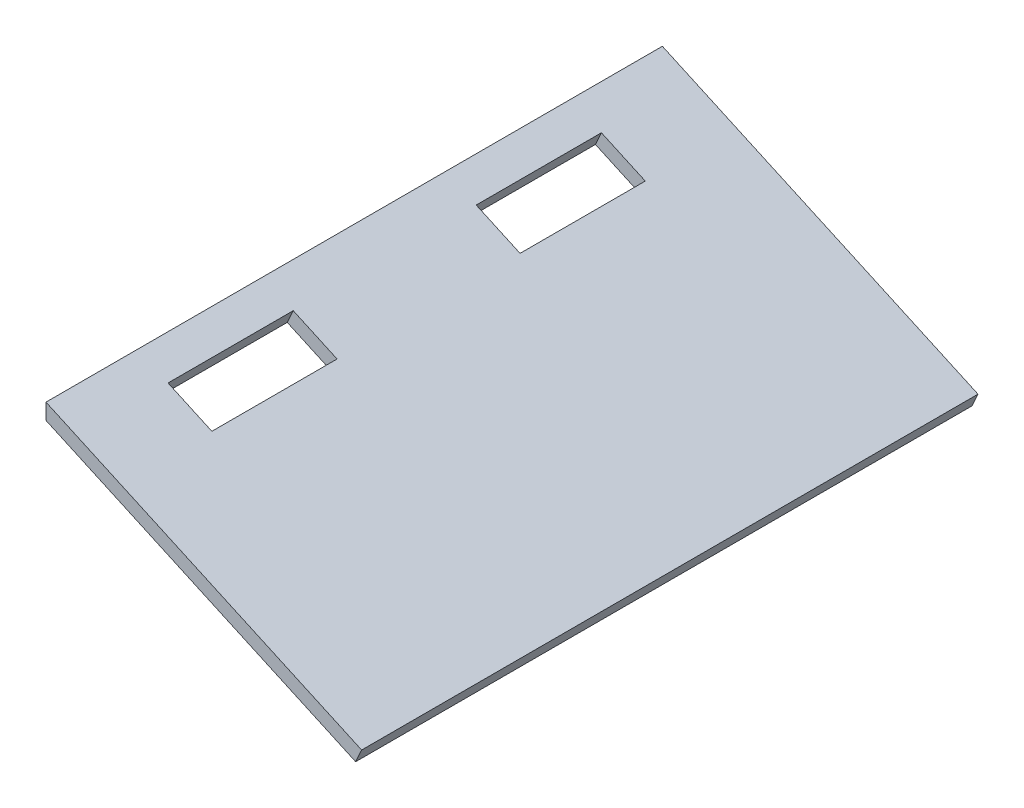
SolidWorks part; units mm, degrees
material "Pine"
ref_plane "Front Plane" through (0, 0, 0) normal (0, 0, 1) x (1, 0, 0)
ref_plane "Top Plane" through (0, 0, 0) normal (0, 1, 0) x (1, 0, 0)
ref_plane "Right Plane" through (0, 0, 0) normal (1, 0, 0) x (0, 0, -1)
sketch "Sketch3" plane through (0, 0, 0) normal (0, 0, 1) x (1, 0, 0)
  line L0 (-108.5345, -3.9032) -> (-108.5345, 1464.0363)
  line L1 (-108.5345, -3.9032) -> (-870.5345, -3.9032)
  line L2 (-870.5345, -3.9032) -> (-870.5345, 625.8363)
  line L3 (-972.1345, 737.9573) -> (-972.1345, 834.2968)
  line L4 (-768.9345, 834.2968) -> (-768.9345, 986.6968)
  line L5 (-972.1345, 834.2968) -> (-768.9345, 834.2968)
  line L6 (-528.0858, 1843.9468) -> (-737.1845, 1843.9468)
  line L7 (-968.4148, 728.977) -> (-874.2542, 634.8165)
  line L8 (-737.1845, 1672.0154) -> (-737.1845, 1762.6932)
  line L9 (-520.195, 1875.6968) -> (-756.2345, 1875.6968)
  line L10 (-112.2542, 1473.0165) -> (-511.2148, 1871.977)
  line L11 (-737.1845, 1692.941) -> (-241.631, 1467.6894)
  line L12 (-596.8655, 1608.234) -> (-737.1845, 983.1768)
  line L13 (-763.9746, 985.3593) -> (-203.7845, 834.2968)
  line L14 (-761.4898, 1669.1128) -> (-638.6318, 1613.2683)
  line L15 (-631.4955, 1598.9249) -> (-768.9345, 986.6968)
  line L16 (-768.9345, 1680.6745) -> (-768.9345, 1862.9968)
  line L17 (-737.1845, 1780.4468) -> (-737.1845, 1843.9468)
  line L18 (-737.1845, 1692.941) -> (-737.1845, 1843.9468) construction
  line L19 (-737.1845, 1692.941) -> (-737.1845, 1762.6932) construction
  line L20 (-838.7845, -3.9032) -> (-838.7845, 834.2968)
  line L21 (-745.0674, 1675.5986) -> (-249.5139, 1450.347) construction
  line L22 (-140.2845, -3.9032) -> (-140.2845, 1456.1455)
  line L23 (-140.2845, 1456.1455) -> (-528.0858, 1843.9468)
  line L24 (-537.8111, 1581.3911) -> (-673.6845, 976.1369)
  line L25 (-768.9345, 966.9663) -> (-203.7845, 814.5663)
  line L26 (-737.1845, 1672.0154) -> (-203.7845, 1429.5608)
  line L27 (-528.0858, 1843.9468) -> (-554.3883, 1780.4468)
  line L28 (-140.2845, 1456.1455) -> (-203.7845, 1429.8429)
  line L29 (-775.2845, -3.9032) -> (-775.2845, 834.2968)
  line L30 (-773.8944, 968.3038) -> (-208.7444, 815.9038) construction
  line L31 (-203.7845, -3.9032) -> (-203.7845, 1429.8429)
  line L32 (-203.7845, 1429.8429) -> (-554.3883, 1780.4468)
  line L33 (-554.3883, 1780.4468) -> (-737.1845, 1780.4468)
  line L34 (-768.9345, 966.9663) -> (-763.9746, 985.3593)
  line L35 (-737.1845, 1762.6932) -> (-369.5099, 1595.5683)
  line L36 (-673.6845, 1733.8295) -> (-599.2171, 1699.9807) construction
  line L37 (-737.1845, 1692.941) -> (-625.4936, 1642.1724) construction
  line L38 (-538.5586, 1578.0615) -> (-673.6845, 976.1369) construction
  line L39 (-600.5166, 1591.9704) -> (-737.1845, 983.1768) construction
  line L40 (-554.3883, 1780.4468) -> (-673.6845, 1780.4468) construction
  line L41 (-203.7845, 91.3468) -> (-203.7845, 1429.8429) construction
  line L42 (-140.2845, 27.8468) -> (-140.2845, 1456.1455) construction
  line L43 (-775.2845, 91.3468) -> (-775.2845, 625.8363) construction
  line L44 (-838.7845, 27.8468) -> (-838.7845, 625.8363) construction
  line L45 (-203.7845, 91.3468) -> (-775.2845, 91.3468) construction
  line L46 (-140.2845, 27.8468) -> (-838.7845, 27.8468) construction
  line L47 (-940.3845, 745.8481) -> (-851.8036, 657.2672) construction
  line L48 (-843.7807, 739.0468) -> (-806.9023, 702.1685) construction
  line L49 (-843.7807, 739.0468) -> (-673.6845, 739.0468) construction
  line L50 (-940.3845, 802.5468) -> (-737.1845, 802.5468) construction
  line L51 (-940.3845, 745.8481) -> (-940.3845, 802.5468) construction
  line L52 (-843.7807, 739.0468) -> (-843.7807, 739.0468) construction
  line L53 (-673.6845, 1733.8295) -> (-673.6845, 1780.4468) construction
  line L54 (-756.2345, 1692.941) -> (-756.2345, 1792.2779) construction
  line L55 (-756.2345, 1792.2779) -> (-361.627, 1612.9108) construction
  line L56 (-673.6845, 739.0468) -> (-673.6845, 976.1369) construction
  line L57 (-737.1845, 802.5468) -> (-737.1845, 983.1768) construction
  line L58 (-768.9345, 986.6968) -> (-203.7845, 834.2968) construction
  line L59 (-203.7845, 834.2968) -> (-208.7444, 815.9038)
  line L60 (-768.9345, 901.198) -> (-203.7845, 748.798)
  line L61 (-846.7775, 922.1894) -> (-163.9675, 738.0608) construction
  line L62 (-768.9345, 966.9663) -> (-208.7444, 815.9038) construction
  line L64 (-808.7515, 1063.2022) -> (-125.9415, 879.0737) construction
  line L65 (-125.9415, 879.0737) -> (-163.9675, 738.0608) construction
  line L66 (-846.7775, 922.1894) -> (-808.7515, 1063.2022) construction
  arc A0 (-108.5345, 1464.0363) -> (-112.2542, 1473.0165) centre (-121.2345, 1464.0363) ccw
  arc A1 (-511.2148, 1871.977) -> (-520.195, 1875.6968) centre (-520.195, 1862.9968) ccw
  arc A2 (-768.9345, 1862.9968) -> (-756.2345, 1875.6968) centre (-756.2345, 1862.9968) cw
  arc A3 (-768.9345, 1680.6745) -> (-761.4898, 1669.1128) centre (-756.2345, 1680.6745) ccw
  arc A4 (-631.4955, 1598.9249) -> (-638.6318, 1613.2683) centre (-643.8871, 1601.7067) ccw
  arc A5 (-972.1345, 737.9573) -> (-968.4148, 728.977) centre (-959.4345, 737.9573) ccw
  arc A6 (-870.5345, 625.8363) -> (-874.2542, 634.8165) centre (-883.2345, 625.8363) ccw
  arc A7 (-737.1845, 1843.9468) -> (-737.1845, 1843.9468) centre (-737.1845, 1843.9468) cw
  arc A8 (-737.1845, 1692.941) -> (-737.1845, 1692.941) centre (-737.1845, 1692.941) ccw
  arc A12 (-140.2845, 1456.1455) -> (-140.2845, 1456.1455) centre (-140.2845, 1456.1455) ccw
  arc A13 (-528.0858, 1843.9468) -> (-528.0858, 1843.9468) centre (-528.0858, 1843.9468) ccw
  arc A14 (-600.5166, 1591.9704) -> (-625.4936, 1642.1724) centre (-643.8871, 1601.7067) ccw construction
  arc A16 (-203.7845, 1429.8429) -> (-203.7845, 1429.8429) centre (-203.7845, 1429.8429) ccw
  arc A17 (-554.3883, 1780.4468) -> (-554.3883, 1780.4468) centre (-554.3883, 1780.4468) ccw
  arc A18 (-673.6845, 1780.4468) -> (-673.6845, 1780.4468) centre (-673.6845, 1780.4468) cw
  arc A19 (-673.6845, 1733.8295) -> (-673.6845, 1733.8295) centre (-673.6845, 1733.8295) ccw
  arc A20 (-838.7845, 625.8363) -> (-851.8036, 657.2672) centre (-883.2345, 625.8363) ccw construction
  arc A21 (-775.2845, 625.8363) -> (-806.9023, 702.1685) centre (-883.2345, 625.8363) ccw construction
  arc A22 (-843.7807, 739.0468) -> (-843.7807, 739.0468) centre (-843.7807, 739.0468) ccw construction
  arc A23 (-940.3845, 745.8481) -> (-940.3845, 745.8481) centre (-940.3845, 745.8481) ccw construction
  arc A24 (-756.2345, 1692.941) -> (-745.0674, 1675.5986) centre (-737.1845, 1692.941) ccw construction
  dimension "D1" = 12.7
  dimension "D2" = 31.75
  dimension "D3" = 63.5
  dimension "D4" = 19.05
  dimension "D5" = 19.05
  dimension "D6" = 63.5
sketch "Sketch6" plane through (0, 0, 0) normal (0, 0, 1) x (1, 0, 0)
  line L0 (-737.1845, 1672.0154) -> (-737.1845, 1692.941)
  line L1 (-737.1845, 1692.941) -> (-320.9649, 1503.7503)
  line L2 (-737.1845, 1672.0154) -> (-328.8479, 1486.4078)
  line L5 (-320.9649, 1503.7503) -> (-328.8479, 1486.4078)
extrude "Boss-Extrude1" add sketch "Sketch6" along normal blind 812.8
sketch "Sketch7" plane through (503.6386, 1108.0049, 0) normal (-0.4138, -0.9104, 0) x (0.9104, -0.4138, 0)
  line L0 (-1362.9929, 0) -> (-914.452, 0)
  line L1 (-914.452, 812.8) -> (-914.452, 0) construction
  line L2 (-1362.9929, 812.8) -> (-1362.9929, 0)
  line L3 (-914.452, 812.8) -> (-914.452, 0)
  line L4 (-1056.1725, 641.35) -> (-1056.1725, 577.85)
  line L5 (-1221.2725, 171.45) -> (-1056.1725, 171.45)
  line L6 (-1221.2725, 171.45) -> (-1221.2725, 234.95)
  line L7 (-1221.2725, 234.95) -> (-1056.1725, 234.95)
  line L8 (-1056.1725, 171.45) -> (-1056.1725, 234.95)
  line L9 (-1221.2725, 577.85) -> (-1056.1725, 577.85)
  line L10 (-1221.2725, 641.35) -> (-1221.2725, 577.85)
  line L11 (-1221.2725, 641.35) -> (-1056.1725, 641.35)
  line L12 (-1362.9929, 812.8) -> (-914.452, 812.8)
sketch "Sketch8" plane through (503.6386, 1108.0049, 0) normal (-0.4138, -0.9104, 0) x (0.9104, -0.4138, 0)
  line L0 (-1263.906, 120.65) -> (-1263.906, 285.75)
  line L1 (-1263.906, 285.75) -> (-1327.406, 285.75)
  line L2 (-1327.406, 285.75) -> (-1327.406, 120.65)
  line L3 (-1327.406, 120.65) -> (-1263.906, 120.65)
  line L4 (-1327.406, 692.15) -> (-1263.906, 692.15)
  line L5 (-1327.406, 527.05) -> (-1327.406, 692.15)
  line L6 (-1263.906, 527.05) -> (-1327.406, 527.05)
  line L7 (-1263.906, 692.15) -> (-1263.906, 527.05)
extrude "Cut-Extrude1" cut sketch "Sketch8" against normal blind 19.05
